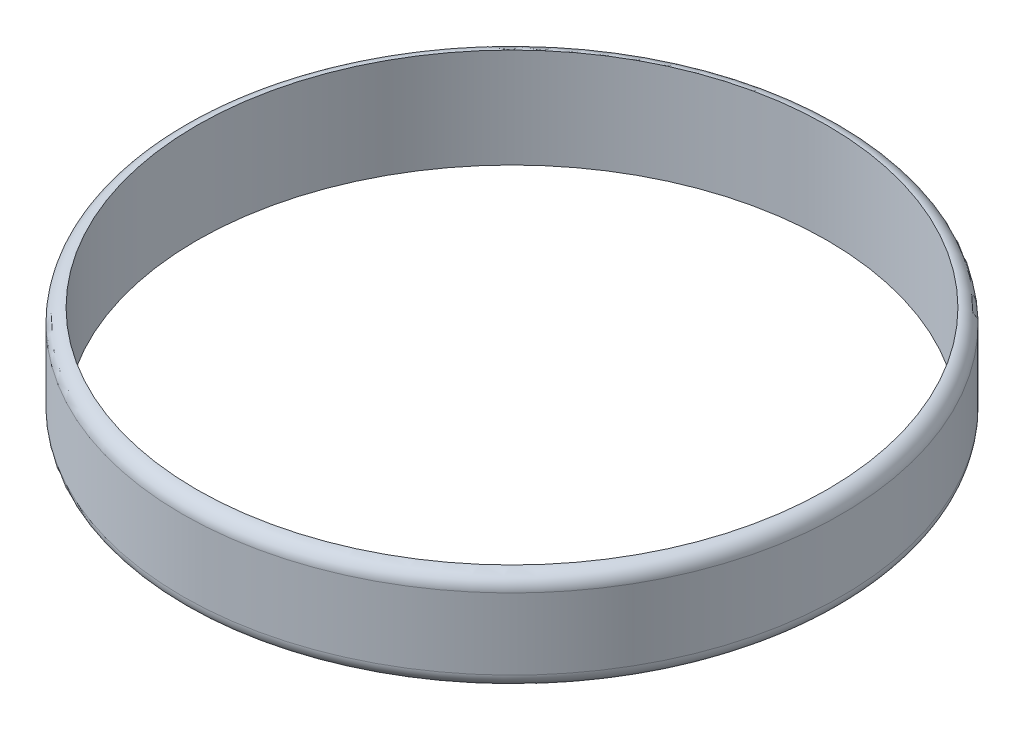
SolidWorks part; units mm, degrees
material "ASTM A36"
ref_plane "Plano frontal" through (0, 0, 0) normal (0, 0, 1) x (1, 0, 0)
ref_plane "Plano superior" through (0, 0, 0) normal (0, 1, 0) x (1, 0, 0)
ref_plane "Plano direito" through (0, 0, 0) normal (1, 0, 0) x (0, 0, -1)
sketch "Esboço1" plane through (0, 0, 0) normal (0, 1, 0) x (1, 0, 0)
  circle A0 centre (0, 0) radius 66.5
  circle A1 centre (0, 0) radius 69.5
  dimension "D1" = 133
  dimension "D2" = 3
extrude "Ressalto-extrusão1" add sketch "Esboço1" along normal mid plane 21
fillet "Filete1" radius 3 2 edges at (0, -10.5, 69.5) (0, 10.5, 69.5)
